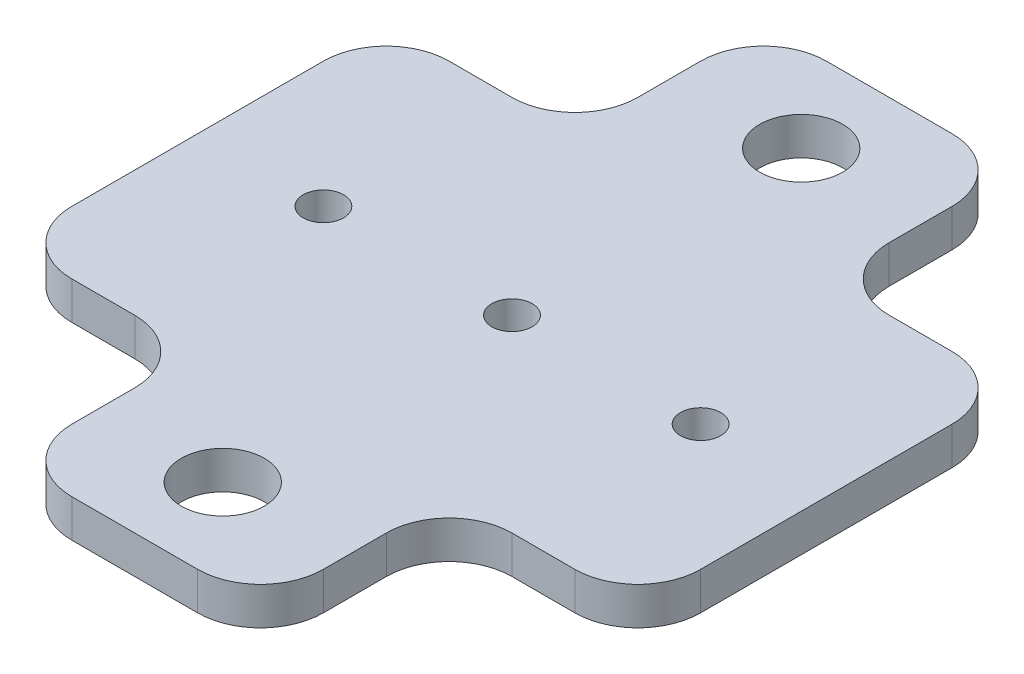
SolidWorks part; units mm, degrees
ref_plane "前视基准面" through (0, 0, 0) normal (0, 0, 1) x (1, 0, 0)
ref_plane "上视基准面" through (0, 0, 0) normal (0, 1, 0) x (1, 0, 0)
ref_plane "右视基准面" through (0, 0, 0) normal (1, 0, 0) x (0, 0, -1)
other "Configuration Table"
sketch "草图1" plane through (0, 0, 0) normal (0, 1, 0) x (1, 0, 0)
  line L0 (10, 15) -> (25, 15)
  line L1 (-10, 30) -> (10, 30)
  line L2 (-10, 30) -> (-10, 15)
  line L3 (-10, -30) -> (10, -30)
  line L4 (10, 30) -> (10, 15)
  line L5 (-10, 30) -> (10, -30) construction
  line L6 (-10, -30) -> (10, 30) construction
  line L7 (-25, 15) -> (-10, 15)
  line L8 (-25, 15) -> (-25, -15)
  line L9 (-25, -15) -> (-10, -15)
  line L10 (25, 15) -> (25, -15)
  line L11 (-25, 15) -> (25, -15) construction
  line L12 (-25, -15) -> (25, 15) construction
  line L13 (-10, -15) -> (-10, -30)
  line L14 (10, -15) -> (25, -15)
  line L15 (10, -15) -> (10, -30)
  point P0 (0, 0)
  point P6 (0, 0)
  dimension "D1" = 60
  dimension "D2" = 30
  dimension "D3" = 20
  dimension "D4" = 50
extrude "凸台-拉伸1" add sketch "草图1" along normal blind 3
fillet "圆角1" radius 5 12 edges at (-25, 1.5, 15) (-10, 1.5, 15) (-10, 1.5, 30) (10, 1.5, 30) (10, 1.5, 15) (25, 1.5, 15) (25, 1.5, -15) (-25, 1.5, -15) (-10, 1.5, -15) (10, 1.5, -15) (10, 1.5, -30) (-10, 1.5, -30)
sketch "草图2" plane through (0, 3, 0) normal (0, 1, 0) x (1, 0, 0)
  line L0 (25, -10) -> (25, 10) construction
  line L1 (15, -15) -> (20, -15) construction
  circle A0 centre (15, 0) radius 1.6
  circle A1 centre (0, 0) radius 1.6
  circle A2 centre (-15, 0) radius 1.6
  dimension "D3" = 3.2
  dimension "D1" = 10
  dimension "D2" = 15
  dimension "D4" = 3
extrude "切除-拉伸1" cut sketch "草图2" against normal blind 10
sketch "草图3" plane through (0, 3, 0) normal (0, 1, 0) x (1, 0, 0)
  line L0 (-5, -30) -> (5, -30) construction
  line L1 (-10, -20) -> (-10, -25) construction
  circle A0 centre (0, -23) radius 3.3
  circle A1 centre (0, 23) radius 3.3
  dimension "D1" = 6.6
  dimension "D2" = 7
  dimension "D3" = 10
  dimension "D4" = 2
extrude "切除-拉伸2" cut sketch "草图3" against normal blind 10
